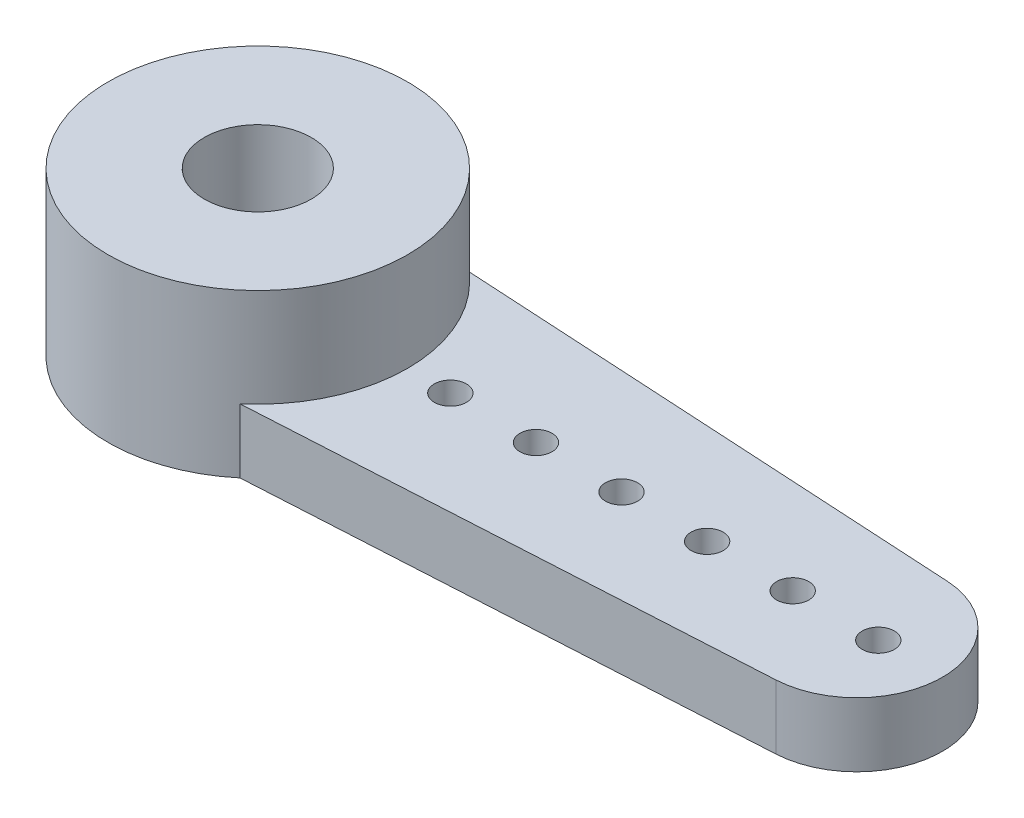
SolidWorks part; units mm, degrees
ref_plane "Front Plane" through (0, 0, 0) normal (0, 0, 1) x (1, 0, 0)
ref_plane "Top Plane" through (0, 0, 0) normal (0, 1, 0) x (1, 0, 0)
ref_plane "Right Plane" through (0, 0, 0) normal (1, 0, 0) x (0, 0, -1)
sketch "Sketch1" plane through (0, 0, 0) normal (0, 1, 0) x (1, 0, 0)
  line L0 (2.2571, 2.675) -> (14.1106, 2)
  line L1 (0, 0) -> (13.9968, 0) construction
  line L2 (14.1106, -2) -> (2.2571, -2.675)
  line L3 (0, 3.5) -> (0, -3.5) construction
  arc A0 (2.2571, 2.675) -> (2.2571, -2.675) centre (0, 0) ccw
  arc A1 (14.1106, 2) -> (14.1106, -2) centre (13.9968, 0) cw
  point P11 (-3.5, 0)
  point P12 (16, 0)
  dimension "D1" = 4
  dimension "D2" = 7
  dimension "D3" = 5.35
  dimension "D4" = 19.5
extrude "Boss-Extrude1" add sketch "Sketch1" along normal blind 1.5
sketch "Sketch2" plane through (0, 1.5, 0) normal (0, 1, 0) x (1, 0, 0)
  circle A0 centre (0, 0) radius 3.5
  arc A1 (2.2571, 2.675) -> (2.2571, -2.675) centre (0, 0) ccw construction
extrude "Boss-Extrude2" add sketch "Sketch2" along normal offset from surface (2.3 mm away) 3.8 up to face at (7.2169, 0, 0)
sketch "Sketch3" plane through (0, 1.5, 0) normal (0, 1, 0) x (1, 0, 0)
  circle A1 centre (4.5, 0) radius 0.375
  circle A8 centre (0, 0) radius 1.25
  circle A10 centre (6.5, 0) radius 0.375
  circle A11 centre (8.5, 0) radius 0.375
  circle A12 centre (10.5, 0) radius 0.375
  circle A13 centre (12.5, 0) radius 0.375
  circle A14 centre (14.5, 0) radius 0.375
  dimension "D1" = 0.75
  dimension "D3" = 2.5
  dimension "D4" = 2
  dimension "D2" = 4.5
extrude "Cut-Extrude1" cut sketch "Sketch3" against normal through all both and the other way through all
ref_axis "Axis1" through (0, 3.99, 0) along (0, -1, 0)
